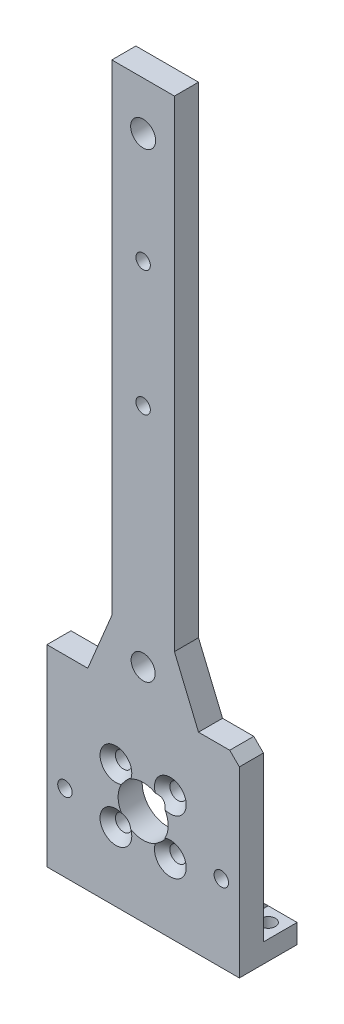
SolidWorks part; units mm, degrees
ref_plane "前视基准面" through (0, 0, 0) normal (0, 0, 1) x (1, 0, 0)
ref_plane "上视基准面" through (0, 0, 0) normal (0, 1, 0) x (1, 0, 0)
ref_plane "右视基准面" through (0, 0, 0) normal (1, 0, 0) x (0, 0, -1)
other "Configuration Table"
sketch "草图1" plane through (0, 0, 0) normal (0, 0, 1) x (1, 0, 0)
  line L0 (-20, 0) -> (20, 0) construction
  line L1 (-20, -20) -> (20, -20)
  line L2 (-20, -20) -> (-20, 20)
  line L3 (-20, 20) -> (20, 20)
  line L4 (20, -20) -> (20, 20)
  line L5 (-20, -20) -> (20, 20) construction
  line L6 (-20, 20) -> (20, -20) construction
  line L7 (0, 20) -> (0, -20) construction
  line L9 (-5.6569, -5.6569) -> (5.6569, -5.6569) construction
  line L10 (-5.6569, -5.6569) -> (-5.6569, 5.6569) construction
  line L11 (-5.6569, 5.6569) -> (5.6569, 5.6569) construction
  line L12 (5.6569, -5.6569) -> (5.6569, 5.6569) construction
  line L13 (-5.6569, -5.6569) -> (5.6569, 5.6569) construction
  line L14 (-5.6569, 5.6569) -> (5.6569, -5.6569) construction
  circle A2 centre (0, 0) radius 5.2
  circle A3 centre (0, 0) radius 8 construction
  circle A4 centre (5.6569, 5.6569) radius 1.6
  circle A5 centre (5.6569, -5.6569) radius 1.6
  circle A6 centre (-5.6569, -5.6569) radius 1.6
  circle A7 centre (-5.6569, 5.6569) radius 1.6
  point P0 (0, 0)
  point P31 (0, 0)
  dimension "D6" = 10.4
  dimension "D7" = 16
  dimension "D8" = 3.2
  dimension "D1" = 40
  dimension "D2" = 40
  dimension "D9" = 4
extrude "凸台-拉伸1" add sketch "草图1" along normal blind 5
hole_wizard "孔1" positions "3D草图1" profile "草图2" legacy end condition through all
sketch3d "3D草图1"
  line L0 (0, 20, 5) -> (0, -20, 5) construction
  line L1 (20, 20, 5) -> (-20, 20, 5) construction
  line L2 (-20, -20, 5) -> (20, -20, 5) construction
  line L3 (-20, 0, 5) -> (20, 0, 5) construction
  line L4 (-20, 20, 5) -> (-20, -20, 5) construction
  line L5 (20, -20, 5) -> (20, 20, 5) construction
  point P0 (16.25, -4, 5)
  point P2 (-16.25, -4, 5)
  dimension "D1" = 16.25
  dimension "D2" = 16.25
  dimension "D3" = 4
  dimension "D4" = 4
sketch "草图2" plane through (16.25, -4, 5) normal (1, 0, 0) x (0, -1, 0)
  line L0 (0, 0) -> (0, 5)
  line L1 (0, 5) -> (1.5, 5)
  line L2 (1.5, 5) -> (1.5, 0)
  line L3 (1.5, 0) -> (0, 0)
  line L4 (0, 110) -> (0, -10) construction
  dimension "直径" = 3
  dimension "深度" = 5
chamfer "倒角1" distance 2 angle 45 1 edges at (20, 20, 2.5)
hole_wizard "M3 十字槽沉头木螺钉的锥形沉头孔2" positions "草图5" profile "草图6" countersink size "M3" standard "GB" end condition through all
sketch "草图5" plane through (0, 0, 5) normal (0, 0, 1) x (1, 0, 0)
  point P0 (-5.6569, 5.6569)
  point P3 (5.6569, 5.6569)
  point P6 (5.6569, -5.6569)
  point P9 (-5.6569, -5.6569)
sketch "草图6" plane through (-5.6569, 5.6569, 5) normal (1, 0, 0) x (0, -1, 0)
  line L0 (0, 0) -> (0, 5)
  line L1 (0, 5) -> (1.7, 5)
  line L2 (1.7, 5) -> (1.7, 1.6)
  line L3 (1.7, 1.6) -> (3.3, 0)
  line L5 (3.3, 0) -> (0, 0)
  line L6 (-1.7, 1.6) -> (-3.3, 0) construction
  line L11 (0, -6.35) -> (0, 107.95) construction
  dimension "通孔孔直径" = 3.4
  dimension "通孔孔深度" = 5
  dimension "近端锥形沉头孔直径" = 6.6
  dimension "近端锥形沉头孔角度" = 90
sketch "草图7" plane through (0, 0, 0) normal (0, 0, -1) x (-1, 0, 0)
  line L0 (0, -20) -> (0, 33.662) construction
  line L1 (20, -20) -> (-20, -20) construction
  line L2 (-18, 20) -> (20, 20) construction
  line L3 (-6.5078, 20) -> (6.5078, 20)
  line L4 (-6.5078, 20) -> (-6.5078, 32) construction
  line L5 (-6.5078, 32) -> (6.5078, 32)
  line L6 (6.5078, 20) -> (6.5078, 32) construction
  line L7 (6.5078, 32) -> (11.5078, 20)
  line L8 (-6.5078, 32) -> (-11.5078, 20)
  line L9 (-6.5078, 26) -> (6.5078, 26) construction
  circle A1 centre (0, 26) radius 2.5
  line M11 (20, 20) -> (-18, 20)
  dimension "D4" = 5
  dimension "D1" = 5
  dimension "D2" = 5
  dimension "D3" = 12
extrude "凸台-拉伸2" add sketch "草图7" against normal up to surface (5 mm away) contours L5 L8 L7 A1 M11 region at (9.0078, 20.2596, 0) up to face at (17.75, -4, 5)
sketch "草图10" plane through (0, -20, 0) normal (0, -1, 0) x (1, 0, 0)
  line L1 (20, 0) -> (11, 0)
  line L2 (20, 0) -> (20, -7)
  line L3 (20, -7) -> (11, -7)
  line L4 (11, 0) -> (11, -7)
  circle A0 centre (17, -4) radius 1.5
  dimension "D5" = 3
  dimension "D1" = 7
  dimension "D2" = 9
  dimension "D3" = 4
  dimension "D4" = 3
extrude "凸台-拉伸4" add sketch "草图10" against normal blind 4
ref_plane "基准面1" through (0, 0, 0) normal (1, 0, 0) x (0, 0, -1)
sketch "草图12" plane through (11, 0, 0) normal (-1, 0, 0) x (0, 0, 1)
  line L0 (-7, -16) -> (0, -9)
  line L1 (0, 20) -> (0, -20) construction
  line L2 (0, -9) -> (0, -16)
  line L3 (0, -16) -> (-7, -16)
  dimension "D1" = 45
extrude "凸台-拉伸6" add sketch "草图12" against normal blind 3
mirror "镜向2" about plane through (0, 0, 0) normal (1, 0, 0) of "凸台-拉伸4", "凸台-拉伸6"
sketch "草图13" plane through (0, 0, 5) normal (0, 0, 1) x (1, 0, 0)
  line L1 (-6.5078, 32) -> (6.5078, 32)
  line L2 (-6.5078, 32) -> (-6.5078, 132)
  line L3 (-6.5078, 132) -> (6.5078, 132)
  line L4 (6.5078, 32) -> (6.5078, 132)
  circle A0 centre (0, 122) radius 2.6
  circle A1 centre (0, 99) radius 1.5
  circle A2 centre (0, 73) radius 1.5
  dimension "D2" = 5.2
  dimension "D6" = 3
  dimension "D7" = 3
  dimension "D1" = 100
  dimension "D3" = 10
  dimension "D4" = 23
  dimension "D5" = 26
extrude "凸台-拉伸7" add sketch "草图13" against normal up to surface (5 mm away) up to face at (-3.9569, 5.6569, 0)
